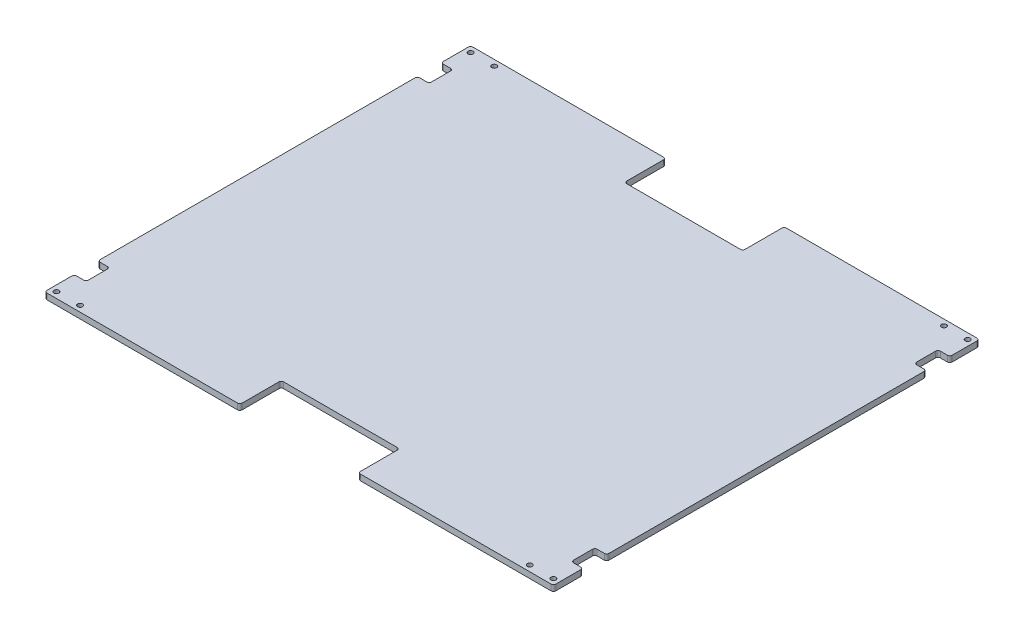
SolidWorks part; units mm, degrees
ref_plane "Front Plane" through (0, 0, 0) normal (0, 0, 1) x (1, 0, 0)
ref_plane "Top Plane" through (0, 0, 0) normal (0, 1, 0) x (1, 0, 0)
ref_plane "Right Plane" through (0, 0, 0) normal (1, 0, 0) x (0, 0, -1)
sketch "Sketch1" plane through (0, 0, 0) normal (0, 1, 0) x (1, 0, 0)
  line L0 (-273.05, 226.06) -> (-273.05, 199.39)
  line L1 (273.05, 226.06) -> (273.05, 199.39)
  line L2 (270.51, 228.6) -> (66.04, 228.6)
  line L3 (-270.51, -228.6) -> (-66.04, -228.6)
  line L4 (-270.51, 196.85) -> (-262.89, 196.85)
  line L5 (-260.35, 194.31) -> (-260.35, 173.99)
  line L6 (-262.89, 171.45) -> (-270.51, 171.45)
  line L7 (-273.05, 168.91) -> (-273.05, -168.91)
  line L8 (0, -55) -> (0, 55) construction
  line L9 (262.89, 171.45) -> (270.51, 171.45)
  line L10 (260.35, 194.31) -> (260.35, 173.99)
  line L11 (270.51, 196.85) -> (262.89, 196.85)
  line L12 (273.05, 168.91) -> (273.05, -168.91)
  line L13 (273.05, 0) -> (-273.05, 0) construction
  line L14 (270.51, -196.85) -> (262.89, -196.85)
  line L15 (262.89, -171.45) -> (270.51, -171.45)
  line L16 (260.35, -194.31) -> (260.35, -173.99)
  line L17 (-260.35, -194.31) -> (-260.35, -173.99)
  line L18 (-270.51, -196.85) -> (-262.89, -196.85)
  line L19 (-262.89, -171.45) -> (-270.51, -171.45)
  line L20 (-273.05, -199.39) -> (-273.05, -226.06)
  line L21 (273.05, -199.39) -> (273.05, -226.06)
  line L22 (63.5, 226.06) -> (63.5, 186.69)
  line L23 (60.96, 184.15) -> (-60.96, 184.15)
  line L24 (-63.5, 186.69) -> (-63.5, 226.06)
  line L25 (-66.04, 228.6) -> (-270.51, 228.6)
  line L26 (-63.5, -186.69) -> (-63.5, -226.06)
  line L27 (60.96, -184.15) -> (-60.96, -184.15)
  line L28 (63.5, -226.06) -> (63.5, -186.69)
  line L29 (66.04, -228.6) -> (270.51, -228.6)
  circle A0 centre (-266.7, 222.25) radius 2.667
  circle A1 centre (266.7, 222.25) radius 2.667
  circle A2 centre (-241.3, 222.25) radius 2.667
  circle A3 centre (241.3, 222.25) radius 2.667
  circle A4 centre (-266.7, -222.25) radius 2.667
  circle A5 centre (266.7, -222.25) radius 2.667
  circle A6 centre (-241.3, -222.25) radius 2.667
  circle A7 centre (241.3, -222.25) radius 2.667
  arc A8 (-273.05, -226.06) -> (-270.51, -228.6) centre (-270.51, -226.06) ccw
  arc A9 (273.05, -226.06) -> (270.51, -228.6) centre (270.51, -226.06) cw
  arc A10 (-273.05, 226.06) -> (-270.51, 228.6) centre (-270.51, 226.06) cw
  arc A11 (273.05, 226.06) -> (270.51, 228.6) centre (270.51, 226.06) ccw
  arc A12 (270.51, 196.85) -> (273.05, 199.39) centre (270.51, 199.39) ccw
  arc A13 (260.35, 194.31) -> (262.89, 196.85) centre (262.89, 194.31) cw
  arc A14 (270.51, 171.45) -> (273.05, 168.91) centre (270.51, 168.91) cw
  arc A15 (262.89, 171.45) -> (260.35, 173.99) centre (262.89, 173.99) cw
  arc A16 (270.51, -171.45) -> (273.05, -168.91) centre (270.51, -168.91) ccw
  arc A17 (262.89, -171.45) -> (260.35, -173.99) centre (262.89, -173.99) ccw
  arc A18 (262.89, -196.85) -> (260.35, -194.31) centre (262.89, -194.31) cw
  arc A19 (270.51, -196.85) -> (273.05, -199.39) centre (270.51, -199.39) cw
  arc A20 (-270.51, -171.45) -> (-273.05, -168.91) centre (-270.51, -168.91) cw
  arc A21 (-270.51, -196.85) -> (-273.05, -199.39) centre (-270.51, -199.39) ccw
  arc A22 (-260.35, -173.99) -> (-262.89, -171.45) centre (-262.89, -173.99) ccw
  arc A23 (-260.35, -194.31) -> (-262.89, -196.85) centre (-262.89, -194.31) cw
  arc A24 (-260.35, 173.99) -> (-262.89, 171.45) centre (-262.89, 173.99) cw
  arc A25 (-273.05, 168.91) -> (-270.51, 171.45) centre (-270.51, 168.91) cw
  arc A26 (-260.35, 194.31) -> (-262.89, 196.85) centre (-262.89, 194.31) ccw
  arc A27 (-273.05, 199.39) -> (-270.51, 196.85) centre (-270.51, 199.39) ccw
  arc A28 (-63.5, 226.06) -> (-66.04, 228.6) centre (-66.04, 226.06) ccw
  arc A29 (63.5, 186.69) -> (60.96, 184.15) centre (60.96, 186.69) cw
  arc A30 (63.5, 226.06) -> (66.04, 228.6) centre (66.04, 226.06) cw
  arc A31 (-60.96, 184.15) -> (-63.5, 186.69) centre (-60.96, 186.69) cw
  arc A32 (-60.96, -184.15) -> (-63.5, -186.69) centre (-60.96, -186.69) ccw
  arc A33 (63.5, -226.06) -> (66.04, -228.6) centre (66.04, -226.06) ccw
  arc A34 (63.5, -186.69) -> (60.96, -184.15) centre (60.96, -186.69) ccw
  arc A35 (-63.5, -226.06) -> (-66.04, -228.6) centre (-66.04, -226.06) cw
  point P44 (-273.05, -228.6)
  point P47 (273.05, -228.6)
  point P50 (-273.05, 228.6)
  point P55 (273.05, 196.85)
  point P58 (260.35, 196.85)
  point P61 (273.05, 171.45)
  point P64 (260.35, 171.45)
  point P67 (273.05, -171.45)
  point P70 (260.35, -171.45)
  point P73 (260.35, -196.85)
  point P76 (273.05, -196.85)
  point P79 (-273.05, -171.45)
  point P82 (-273.05, -196.85)
  point P85 (-260.35, -171.45)
  point P88 (-260.35, -196.85)
  point P91 (-260.35, 171.45)
  point P94 (-273.05, 171.45)
  point P97 (-260.35, 196.85)
  point P100 (-273.05, 196.85)
  point P104 (0, 0)
  point P107 (-63.5, 228.6)
  point P110 (63.5, 184.15)
  point P113 (63.5, 228.6)
  point P116 (-63.5, 184.15)
  point P129 (-63.5, -184.15)
  point P130 (63.5, -228.6)
  point P131 (63.5, -184.15)
  point P132 (-63.5, -228.6)
  point P133 (-382.0806, 23.3806)
  point P134 (0, 0)
  dimension "D1" = 533.4
  dimension "D3" = 5.334
  dimension "D4" = 25.4
  dimension "D5" = 25.4
  dimension "D8" = 533.4
  dimension "D9" = 6.35
  dimension "D10" = 6.35
  dimension "D11" = 444.5
  dimension "D14" = 5.334
  dimension "D19" = 2.54
  dimension "D23" = 2.54
  dimension "D2" = 457.2
  dimension "D6" = 25.4
  dimension "D7" = 25.4
  dimension "D12" = 6.35
  dimension "D13" = 6.35
  dimension "D15" = 31.75
  dimension "D16" = 12.7
  dimension "D17" = 25.4
  dimension "D18" = 228.6
  dimension "D20" = 127
  dimension "D21" = 63.5
  dimension "D22" = 44.45
  dimension "D24" = 2.54
extrude "Boss-Extrude1" add sketch "Sketch1" along normal blind 6.35
